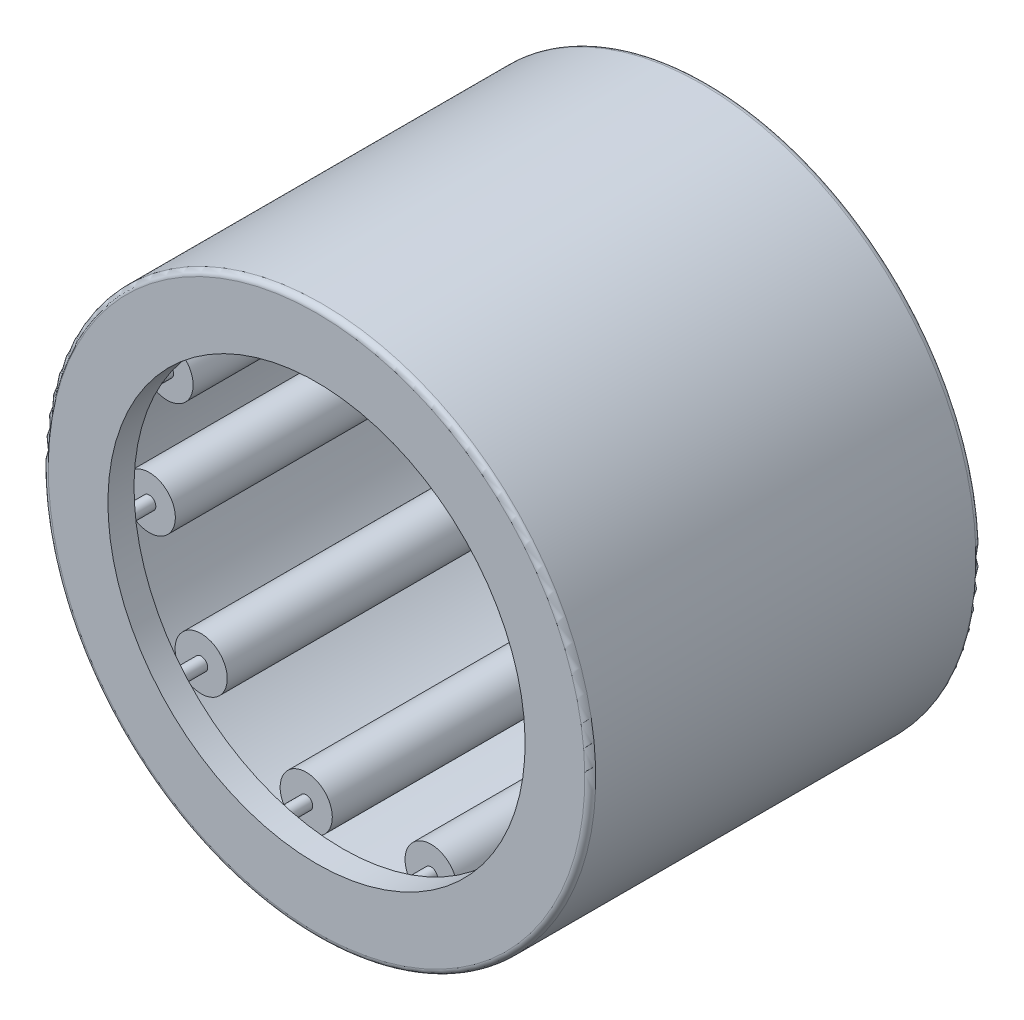
SolidWorks part; units mm, degrees
ref_plane "Front Plane" through (0, 0, 0) normal (0, 0, 1) x (1, 0, 0)
ref_plane "Top Plane" through (0, 0, 0) normal (0, 1, 0) x (1, 0, 0)
ref_plane "Right Plane" through (0, 0, 0) normal (1, 0, 0) x (0, 0, -1)
sketch "Sketch1" plane through (0, 0, 0) normal (1, 0, 0) x (0, 0, -1)
  line L0 (-5, 0) -> (5, 0) construction
  line L1 (0, 0) -> (0, 7) construction
  line L2 (-5, 0) -> (-5, 7) construction
  line L3 (-5, 7) -> (5, 7)
  line L4 (5, 7) -> (5, 0) construction
  line L5 (5, 0) -> (4.3333, 0) construction
  line L6 (4.3333, 0) -> (4.3333, 6.3333) construction
  line L7 (4.3333, 6.3333) -> (-4.3333, 6.3333)
  line L8 (-4.3333, 6.3333) -> (-4.3333, 0) construction
  line L9 (-4.3333, 0) -> (-5, 0) construction
  line L10 (-5, 7) -> (-5, 5.3333)
  line L11 (-5, 5.3333) -> (-4.3333, 5.3333)
  line L12 (-4.3333, 5.3333) -> (-4.3333, 6.3333)
  line L13 (4.3333, 7) -> (4.3333, 6.3333) construction
  line L14 (4.3333, 6.3333) -> (4.3333, 5.3333)
  line L15 (4.3333, 5.3333) -> (5, 5.3333)
  line L16 (5, 5.3333) -> (5, 7)
  line L17 (4.3333, 6.3333) -> (4.3333, 5.6667) construction
  line L18 (4.3333, 5.6667) -> (4.3333, 5) construction
  line L19 (4.3333, -6.3333) -> (4.3333, -5.6667) construction
  line L20 (4.3333, -7) -> (4.3333, -6.3333) construction
  line L21 (5, -5.3333) -> (5, -7) construction
  line L22 (4.3333, -5.3333) -> (5, -5.3333) construction
  line L23 (4.3333, -6.3333) -> (4.3333, -5.3333) construction
  line L24 (-4.3333, -5.3333) -> (-4.3333, -6.3333) construction
  line L25 (-5, -5.3333) -> (-4.3333, -5.3333) construction
  line L26 (-5, -7) -> (-5, -5.3333) construction
  line L27 (4.3333, -6.3333) -> (-4.3333, -6.3333) construction
  line L28 (-5, -7) -> (5, -7) construction
  point P4 (0, 5)
  dimension "C | Width" = 10
  dimension "Fw | ID" = 10
  dimension "D | OD" = 14
sketch "Sketch7" plane through (0, 0, 0) normal (1, 0, 0) x (0, 0, -1)
  line L0 (-5, 7) -> (-5, 5.3333) construction
  line L1 (-5, 5.3333) -> (-4.3333, 5.3333) construction
  line L2 (-4.3333, 5.3333) -> (-4.3333, 6.3333) construction
  line L3 (4.3333, 6.3333) -> (-4.3333, 6.3333) construction
  line L4 (4.3333, 6.3333) -> (4.3333, 5.3333) construction
  line L5 (4.3333, 5.3333) -> (5, 5.3333) construction
  line L6 (5, 5.3333) -> (5, 7) construction
  line L8 (-5, 7) -> (5, 7) construction
  line L9 (-5, 7) -> (-5, 5.3333)
  line L10 (-5, 5.3333) -> (-4.3333, 5.3333)
  line L13 (-4.3333, 5.3333) -> (-4.3333, 6.3333)
  line L16 (4.3333, 6.3333) -> (-4.3333, 6.3333)
  line L17 (4.3333, 6.3333) -> (4.3333, 5.3333)
  line L18 (4.3333, 5.3333) -> (5, 5.3333)
  line L19 (5, 5.3333) -> (5, 7)
  line L20 (-5, 7) -> (5, 7)
revolve "Revolve1" add sketch "Sketch7" angle 360 about L0
sketch "Sketch2" plane through (0, 0, 0) normal (1, 0, 0) x (0, 0, -1)
  line L0 (-5, 5.3333) -> (-4.3333, 5.3333) construction
  line L1 (-3.6667, 5.6667) -> (3.6667, 5.6667) construction
  line L2 (-3.6667, 5.6667) -> (-3.6667, 6.3333) construction
  line L3 (-3.6667, 6.3333) -> (3.6667, 6.3333)
  line L4 (3.6667, 5.6667) -> (3.6667, 6.3333) construction
  line L5 (4.3333, 5.3333) -> (5, 5.3333) construction
  line L6 (-4.3333, 5.6667) -> (-3.6667, 5.6667) construction
  line L7 (3.6667, 5.6667) -> (4.3333, 5.6667) construction
  line L8 (5, 7) -> (5, 0) construction
  line L9 (-3.6667, 5.8333) -> (-3.6667, 5.5) construction
  line L10 (-4.3333, 5.6667) -> (-4.3333, 5.3333) construction
  line L11 (-3.6667, 6.3333) -> (-3.6667, 5.8333)
  line L12 (3.6667, 6.3333) -> (3.6667, 5.8333)
  line L13 (3.6667, 5.8333) -> (-3.6667, 5.8333)
  line L14 (0, 6.3333) -> (0, 5) construction
  line L16 (-3.6667, 5.5) -> (-4.3333, 5.5) construction
  line L17 (0, 0) -> (5, 0) construction
  line L18 (-3.6667, -5.5) -> (-4.3333, -5.5) construction
  line L19 (0, -6.3333) -> (0, -5) construction
  line L20 (-4.3333, -5.6667) -> (-4.3333, -5.3333) construction
  line L21 (-3.6667, -5.8333) -> (-3.6667, -5.5) construction
  line L22 (3.6667, -5.6667) -> (4.3333, -5.6667) construction
  line L23 (-4.3333, -5.6667) -> (-3.6667, -5.6667) construction
  line L24 (3.6667, -5.6667) -> (3.6667, -6.3333) construction
  line L25 (-3.6667, -5.6667) -> (-3.6667, -6.3333) construction
  line L26 (-3.6667, -5.6667) -> (3.6667, -5.6667) construction
  line L27 (3.6667, -5.8333) -> (-3.6667, -5.8333) construction
  line L28 (3.6667, -6.3333) -> (3.6667, -5.8333) construction
  line L29 (-3.6667, -6.3333) -> (-3.6667, -5.8333) construction
  line L30 (-3.6667, -6.3333) -> (3.6667, -6.3333) construction
  line L33 (4.3333, 6.3333) -> (-4.3333, 6.3333) construction
  line L34 (4.3333, 6.3333) -> (4.3333, 5.3333) construction
  line L35 (-4.3333, 5.3333) -> (-4.3333, 6.3333) construction
  line L36 (0, 0) -> (0, 7) construction
  point P16 (0, 5.6667)
revolve "Revolve2" add sketch "Sketch2" angle 360 about L1
sketch "Sketch3" plane through (0, 0, 0) normal (1, 0, 0) x (0, 0, -1)
  line L1 (-4.3333, 5.6667) -> (4.3333, 5.6667)
  line L2 (-4.3333, 5.6667) -> (-4.3333, 5.8333)
  line L3 (-4.3333, 5.8333) -> (4.3333, 5.8333)
  line L4 (4.3333, 5.6667) -> (4.3333, 5.8333)
  line L5 (0, 0) -> (5, 0) construction
  line L7 (4.3333, -5.6667) -> (4.3333, -5.8333) construction
  line L8 (-4.3333, -5.8333) -> (4.3333, -5.8333) construction
  line L9 (-4.3333, -5.6667) -> (-4.3333, -5.8333) construction
  line L10 (-4.3333, -5.6667) -> (4.3333, -5.6667) construction
  line L11 (4.3333, 6.3333) -> (4.3333, 5.3333) construction
  line L12 (5, 7) -> (5, 0) construction
revolve "Revolve3" add sketch "Sketch3" angle 360 about L1
ref_axis "Axis1" through (0, 5.3333, 5) along (0, 1, 0)
pattern_circular "CirPattern1" count 11 every 32.727 about axis through (0, 0, 5) along (0, 0, -1) of bodies 166 167
fillet "Fillet1" radius 0.14 2 edges at (0, -7, -5) (0, -7, 5)
sketch "Front View" plane through (0, 0, 0) normal (0, 0, 1) x (1, 0, 0)
  circle A0 centre (0, 0) radius 5 construction
  circle A1 centre (0, 0) radius 7 construction
  dimension "ID" = 10
  dimension "OD" = 14
sketch "Right View" plane through (0, 0, 0) normal (1, 0, 0) x (0, 0, -1)
  line L0 (-5, 7) -> (5, 7) construction
  line L1 (-5, 7) -> (5, 7) construction
  line L2 (0, 0) -> (0, 7) construction
  point P4 (0, 7)
  dimension "Width" = 10
equation "\"Rollers@CirPattern1\"  = \"OD@Sketch1\"*.75"
equation "\"D1@Fillet1\" = \"D | OD@Sketch1\" * .01"
equation "\"Angle@CirPattern1\"=360 / \"Rollers@CirPattern1\""
equation "\"ID@Front View\" = \"Fw | ID@Sketch1\""
equation "\"OD@Front View\" = \"D | OD@Sketch1\""
equation "\"Width@Right View\" = \"C | Width@Sketch1\""
